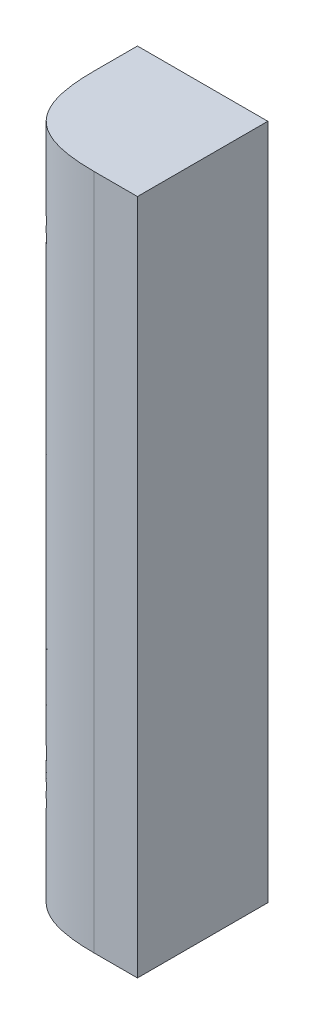
SolidWorks part; units mm, degrees
ref_plane "Front Plane" through (0, 0, 0) normal (0, 0, 1) x (1, 0, 0)
ref_plane "Top Plane" through (0, 0, 0) normal (0, 1, 0) x (1, 0, 0)
ref_plane "Right Plane" through (0, 0, 0) normal (1, 0, 0) x (0, 0, -1)
sketch "Sketch1" plane through (0, 0, 0) normal (0, 1, 0) x (1, 0, 0)
  line L1 (0, 0) -> (36, 0)
  line L2 (0, 0) -> (0, 36)
  line L3 (0, 36) -> (36, 36)
  line L4 (36, 0) -> (36, 36)
  dimension "D1" = 36
  dimension "D2" = 36
extrude "Boss-Extrude1" add sketch "Sketch1" along normal blind 186.9
fillet "Fillet1" radius 24 1 edges at (0, 93.45, 0) conic rho 0.55
